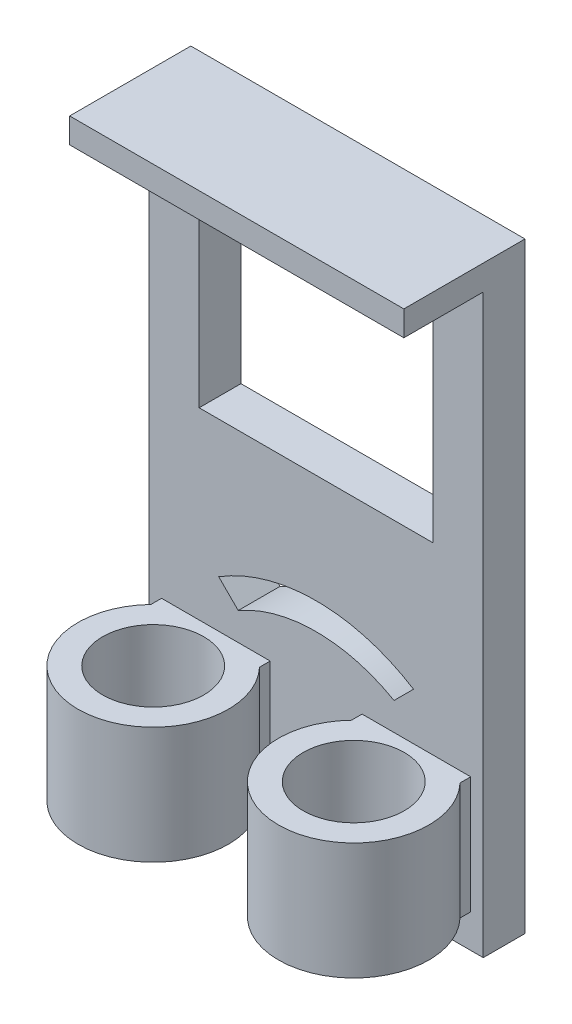
SolidWorks part; units mm, degrees
ref_plane "Front Plane" through (0, 0, 0) normal (0, 0, 1) x (1, 0, 0)
ref_plane "Top Plane" through (0, 0, 0) normal (0, 1, 0) x (1, 0, 0)
ref_plane "Right Plane" through (0, 0, 0) normal (1, 0, 0) x (0, 0, -1)
sketch "Sketch1" plane through (0, 0, 0) normal (0, 0, 1) x (1, 0, 0)
  line L1 (20, -20) -> (-20, -20)
  line L2 (20, -20) -> (20, 20)
  line L3 (20, 20) -> (-20, 20)
  line L4 (-20, -20) -> (-20, 20)
  line L5 (20, -20) -> (-20, 20) construction
  line L6 (20, 20) -> (-20, -20) construction
  point P0 (0, 0)
  dimension "D1" = 40
extrude "Boss-Extrude2" add sketch "Sketch1" along normal blind 2
sketch "Sketch2" plane through (0, 0, 2) normal (0, 0, 1) x (1, 0, 0)
  line L0 (-12, 0) -> (-12, 10) construction
  line L1 (0, 0) -> (-12, 0) construction
  line L2 (-15, 12) -> (-9, 12)
  line L3 (-15, 12) -> (-15, 8)
  line L4 (-15, 8) -> (-9, 8)
  line L5 (-9, 12) -> (-9, 8)
  line L6 (-15, 12) -> (-9, 8) construction
  line L7 (-15, 8) -> (-9, 12) construction
  point P1 (-12, 10)
  dimension "D1" = 10
  dimension "D2" = 4
  dimension "D3" = 6
  dimension "D4" = 12
extrude "Boss-Extrude5" add sketch "Sketch2" along normal blind 3
sketch "Sketch4" plane through (0, 12, 0) normal (0, 1, 0) x (1, 0, 0)
  line L1 (-9, -5) -> (-15, -5) construction
  circle A0 centre (-12, -6.6) radius 1.6
  circle A1 centre (-12, -6.6) radius 3.5
  point P9 (-12, -5)
  dimension "D1" = 3.2
  dimension "D2" = 7
  dimension "D3" = 1.6
extrude "Boss-Extrude6" add sketch "Sketch4" against normal blind 4
ref_plane "Plane2" through (0, 3, 0) normal (0, -1, 0) x (-1, 0, 0)
mirror "Mirror2" about plane through (0, 0, 0) normal (1, 0, 0) of "Boss-Extrude5", "Boss-Extrude6" second plane through (0, 3, 0) second plane normal (0, -1, 0)
sketch "Sketch6" plane through (0, 0, 2) normal (0, 0, 1) x (1, 0, 0)
  line L0 (-20, 20) -> (-15, 20)
  line L1 (20, 20) -> (-20, 20) construction
  line L2 (-15, 20) -> (-15, -20)
  line L3 (-20, -20) -> (20, -20) construction
  line L4 (-15, -20) -> (-20, -20)
  line L5 (-20, -20) -> (-20, 20)
  line L6 (20, 20) -> (15, 20)
  line L7 (15, 20) -> (15, -20)
  line L8 (15, -20) -> (20, -20)
  line L9 (20, -20) -> (20, 20)
  dimension "D1" = 5
  dimension "D2" = 5
  dimension "D4" = 5
extrude "Cut-Extrude1" [suppressed] cut sketch "Sketch6" against normal blind 3 contours L5 L0 L2 L4 | L9 L6 L7 L8
sketch "Sketch7" plane through (0, 0, 2) normal (0, 0, 1) x (1, 0, 0)
  line L0 (0, 0) -> (0, -15)
  line L1 (0, 0) -> (0, 7) construction
  line L2 (-8, 0) -> (8, 0) construction
  line L3 (9.3246, 1.3246) -> (11.6575, 3.6575)
  line L4 (-9.3246, 1.3246) -> (-11.6575, 3.6575)
  line L5 (-8, 0) -> (-9.3246, 1.3246) construction
  line L6 (8, 0) -> (9.3246, 1.3246) construction
  arc A0 (11.6575, 3.6575) -> (-11.6575, 3.6575) centre (0, -15) ccw
  arc A1 (9.3246, 1.3246) -> (-9.3246, 1.3246) centre (0, -15) ccw
  arc A2 (-9.3246, 1.3246) -> (9.3246, 1.3246) centre (0, -15) ccw construction
  arc A3 (-11.6575, 3.6575) -> (11.6575, 3.6575) centre (0, -15) ccw construction
  point P9 (0, 0)
  dimension "D1" = 15
  dimension "D2" = 7
  dimension "D3" = 3.2
  dimension "D4" = 8
  dimension "D5" = 45
  dimension "D6" = 45
extrude "Cut-Extrude2" cut sketch "Sketch7" against normal blind 2 contours A1 L3 A0 L4 region at (0, 4.477, 2)
sketch "Sketch8" plane through (0, 0, 0) normal (0, 0, -1) x (-1, 0, 0)
  line L0 (0, 0) -> (0, -10) construction
  circle A0 centre (0, -10) radius 1.6
  dimension "D1" = 10
  dimension "D2" = 3.2
extrude "Cut-Extrude3" cut sketch "Sketch8" against normal blind 2
sketch "Sketch18" plane through (0, 20, 0) normal (0, 1, 0) x (1, 0, 0)
  line L0 (20, -2) -> (-20, -2) construction
  line L1 (-20, 0) -> (-14, 0)
  line L2 (-20, 0) -> (-20, -2)
  line L3 (-20, -2) -> (-14, -2)
  line L4 (-14, 0) -> (-14, -2)
  line L6 (20, -2) -> (14, -2)
  line L7 (20, -2) -> (20, 0)
  line L8 (20, 0) -> (14, 0)
  line L9 (14, -2) -> (14, 0)
  line L10 (20, 0) -> (-20, 0) construction
  line M5 (20, 0) -> (-20, 0)
  line M6 (-20, 0) -> (-20, -2)
  line M7 (-20, -2) -> (20, -2)
  line M8 (20, -2) -> (20, 0)
  dimension "D2" = 6
  dimension "D1" = 6
extrude "Boss-Extrude10" add sketch "Sketch18" along normal blind 32 contours M7 M8 M5 | M6 M7 region at (-17, 20, 1) region at (17, 20, 1)
sketch "Sketch19" plane through (0, 52, 0) normal (0, 1, 0) x (1, 0, 0)
  line L13 (-20, 0) -> (20, 0)
  line L14 (-20, 0) -> (-20, -3.5)
  line L15 (-20, -3.5) -> (20, -3.5)
  line L16 (20, 0) -> (20, -3.5)
  line M10 (-14, 0) -> (-20, 0)
  line M11 (-20, 0) -> (-20, -2)
  line M12 (-20, -2) -> (-14, -2)
  dimension "D2" = 40
  dimension "D1" = 3.5
extrude "Boss-Extrude11" add sketch "Sketch19" against normal blind 3 contours M12 | M12 M10 M11 region at (0, 52, 1.75)
sketch "Sketch20" plane through (0, -6, 0) normal (0, -1, 0) x (1, 0, 0)
  line L3 (-9, 2) -> (-9, 4.7972)
  line L4 (-15, 4.7972) -> (-15, 2)
  line L5 (-15, 2) -> (-9, 2)
  line L6 (-9, 2) -> (-9, 4.7972)
  line L7 (-15, 4.7972) -> (-15, 2)
  line L8 (-15, 2) -> (-9, 2)
  line L9 (9, 4.7972) -> (9, 2)
  line L10 (9, 2) -> (15, 2)
  line L11 (15, 2) -> (15, 4.7972)
  line L12 (9, 4.7972) -> (9, 2)
  line L13 (9, 2) -> (15, 2)
  line L14 (15, 2) -> (15, 4.7972)
  circle A0 centre (-12, 6.6) radius 1.6 construction
  arc A1 (-9, 4.7972) -> (-15, 4.7972) centre (-12, 6.6) ccw
  arc A2 (-9, 4.7972) -> (-15, 4.7972) centre (-12, 6.6) ccw
  arc A3 (15, 4.7972) -> (9, 4.7972) centre (12, 6.6) ccw
  arc A4 (15, 4.7972) -> (9, 4.7972) centre (12, 6.6) ccw
  circle A5 centre (-12, 6.6) radius 1.6
  circle A6 centre (12, 6.6) radius 1.6 construction
  circle A7 centre (12, 6.6) radius 1.6
  dimension "D1" = 0
  dimension "D2" = 0
extrude "Boss-Extrude12" add sketch "Sketch20" along normal blind 10
sketch "Sketch21" plane through (0, 12, 0) normal (0, 1, 0) x (1, 0, 0)
  line L0 (9, -2) -> (9, -4.7972) construction
  line L1 (15, -4.7972) -> (15, -2) construction
  line L2 (15, -2) -> (9, -2) construction
  line L3 (-9, -4.7972) -> (-9, -2) construction
  line L4 (-9, -2) -> (-15, -2) construction
  line L5 (-15, -2) -> (-15, -4.7972) construction
  line L6 (9, -2) -> (9, -4.7972)
  line L7 (15, -4.7972) -> (15, -2)
  line L8 (15, -2) -> (9, -2)
  line L9 (-9, -4.7972) -> (-9, -2)
  line L10 (-9, -2) -> (-15, -2)
  line L11 (-15, -2) -> (-15, -4.7972)
  arc A0 (9, -4.7972) -> (15, -4.7972) centre (12, -6.6) ccw construction
  arc A1 (-15, -4.7972) -> (-9, -4.7972) centre (-12, -6.6) ccw construction
  circle A2 centre (-12, -6.6) radius 1.6 construction
  circle A3 centre (12, -6.6) radius 1.6 construction
  arc A4 (9, -4.7972) -> (15, -4.7972) centre (12, -6.6) ccw
  arc A5 (-15, -4.7972) -> (-9, -4.7972) centre (-12, -6.6) ccw
  circle A6 centre (-12, -6.6) radius 1.6
  circle A7 centre (12, -6.6) radius 1.6
sketch "Sketch22" plane through (0, -2, 0) normal (0, 1, 0) x (1, 0, 0)
  line L3 (9, -2) -> (9, -4.7972)
  line L4 (15, -4.7972) -> (15, -2)
  line L5 (15, -2) -> (9, -2)
  line L6 (9, -2) -> (9, -4.7972)
  line L7 (15, -4.7972) -> (15, -2)
  line L8 (15, -2) -> (9, -2)
  line L9 (-9, -4.7972) -> (-9, -2)
  line L10 (-9, -2) -> (-15, -2)
  line L11 (-15, -2) -> (-15, -4.7972)
  line L12 (-9, -4.7972) -> (-9, -2)
  line L13 (-9, -2) -> (-15, -2)
  line L14 (-15, -2) -> (-15, -4.7972)
  circle A0 centre (12, -6.6) radius 1.6 construction
  arc A1 (9, -4.7972) -> (15, -4.7972) centre (12, -6.6) ccw
  arc A2 (9, -4.7972) -> (15, -4.7972) centre (12, -6.6) ccw
  circle A3 centre (12, -6.6) radius 1.6
  circle A4 centre (-12, -6.6) radius 1.6 construction
  arc A5 (-15, -4.7972) -> (-9, -4.7972) centre (-12, -6.6) ccw
  arc A6 (-15, -4.7972) -> (-9, -4.7972) centre (-12, -6.6) ccw
  circle A7 centre (-12, -6.6) radius 1.6
  dimension "D1" = 0
  dimension "D2" = 0
extrude "Cut-Extrude4" cut sketch "Sketch22" against normal blind 7
sketch "Sketch23" plane through (0, -16, 0) normal (0, -1, 0) x (1, 0, 0)
  line L0 (-15, 2) -> (-9, 2) construction
  line L1 (-20, 2) -> (20, 2) construction
  line L2 (-15, 2) -> (-9, 2)
  line L3 (-17, 2) -> (-7, 2)
  line L4 (-7, 2) -> (-7, 3.9098)
  line L5 (-17, 2) -> (-17, 3.9098)
  line L6 (0, -5.555) -> (0, 5.555) construction
  line L7 (17, 2) -> (17, 3.9098)
  line L8 (7, 2) -> (7, 3.9098)
  line L9 (17, 2) -> (7, 2)
  line L10 (15, 2) -> (9, 2)
  circle A0 centre (-12, 9.5) radius 6.05
  arc A1 (-7, 3.9098) -> (-17, 3.9098) centre (-12, 9.5) ccw
  arc A2 (7, 3.9098) -> (17, 3.9098) centre (12, 9.5) cw
  circle A3 centre (12, 9.5) radius 6.05
  point P10 (-12, 2)
  point P11 (-12, 2)
  line M8 (-15, 2) -> (-9, 2)
  line M9 (-9, 2) -> (-9, 4.7972)
  line M11 (-15, 4.7972) -> (-15, 2)
  dimension "D1" = 12.1
  dimension "D2" = 15
  dimension "D3" = 10
extrude "Boss-Extrude14" add sketch "Sketch23" against normal blind 14 contours L4 A1 L5 L3 A0 M11 M9 | A0 M11 M8 M9 | A2 L8 L9 L7 A3 region at (-12, -16, 2.8701) region at (-16, -16, 2.2121) region at (16, -16, 2.2121)
extrude "Cut-Extrude5" cut sketch "Sketch21" against normal blind 10
sketch "Sketch24" plane through (0, -9, 0) normal (0, 1, 0) x (1, 0, 0)
  line L2 (9, -4.2462) -> (9, -4.7972)
  line L3 (15, -4.7972) -> (15, -4.2462)
  line L4 (9, -4.2462) -> (9, -4.7972)
  line L5 (15, -4.7972) -> (15, -4.2462)
  line L6 (-9, -4.7972) -> (-9, -4.2462)
  line L7 (-15, -4.2462) -> (-15, -4.7972)
  line L8 (-9, -4.7972) -> (-9, -4.2462)
  line L9 (-15, -4.2462) -> (-15, -4.7972)
  arc A2 (15, -4.2462) -> (9, -4.2462) centre (12, -9.5) ccw
  arc A3 (9, -4.7972) -> (15, -4.7972) centre (12, -6.6) ccw
  arc A4 (15, -4.2462) -> (9, -4.2462) centre (12, -9.5) ccw
  arc A5 (9, -4.7972) -> (15, -4.7972) centre (12, -6.6) ccw
  arc A6 (-9, -4.2462) -> (-15, -4.2462) centre (-12, -9.5) ccw
  arc A7 (-15, -4.7972) -> (-9, -4.7972) centre (-12, -6.6) ccw
  arc A8 (-9, -4.2462) -> (-15, -4.2462) centre (-12, -9.5) ccw
  arc A9 (-15, -4.7972) -> (-9, -4.7972) centre (-12, -6.6) ccw
  dimension "D1" = 0
  dimension "D2" = 0
extrude "Cut-Extrude7" cut sketch "Sketch24" against normal blind 22
sketch "Sketch25" plane through (0, -16, 0) normal (0, -1, 0) x (1, 0, 0)
  line L3 (-17, 2) -> (-7, 2)
  line L4 (-7, 2) -> (-7, 3.9098)
  line L5 (-17, 3.9098) -> (-17, 2)
  line L6 (-17, 2) -> (-7, 2)
  line L7 (-7, 2) -> (-7, 3.9098)
  line L8 (-17, 3.9098) -> (-17, 2)
  line L12 (7, 3.9098) -> (7, 2)
  line L13 (7, 2) -> (17, 2)
  line L14 (17, 2) -> (17, 3.9098)
  line L15 (7, 3.9098) -> (7, 2)
  line L16 (7, 2) -> (17, 2)
  line L17 (17, 2) -> (17, 3.9098)
  arc A1 (-7, 3.9098) -> (-17, 3.9098) centre (-12, 9.5) ccw
  arc A2 (-7, 3.9098) -> (-17, 3.9098) centre (-12, 9.5) ccw
  arc A4 (17, 3.9098) -> (7, 3.9098) centre (12, 9.5) ccw
  arc A5 (17, 3.9098) -> (7, 3.9098) centre (12, 9.5) ccw
  dimension "D1" = 0
  dimension "D2" = 0
sketch "Sketch26" plane through (0, -2, 0) normal (0, 1, 0) x (1, 0, 0)
  line L0 (-16, -2) -> (-8, -2) construction
  line L1 (-16, -2) -> (-16, -6.5)
  line L2 (-8, -2) -> (-8, -6.5)
  line L3 (-7, -2) -> (-17, -2)
  line L4 (-17, -2) -> (-17, -3.9098)
  line L5 (-7, -3.9098) -> (-7, -2)
  line L6 (-7, -2) -> (-17, -2)
  line L8 (-7, -3.9098) -> (-7, -2)
  line L9 (-16, -2) -> (-8, -2)
  line L10 (0, -9.35) -> (0, 9.35) construction
  line L11 (16, -2) -> (16, -6.5)
  line L12 (16, -2) -> (8, -2)
  line L13 (8, -2) -> (8, -6.5)
  circle A0 centre (-12, -9.5) radius 3.15
  arc A1 (-17, -3.9098) -> (-7, -3.9098) centre (-12, -9.5) ccw
  arc A3 (-16, -6.5) -> (-8, -6.5) centre (-12, -9.5) ccw
  circle A4 centre (12, -9.5) radius 3.15
  arc A5 (16, -6.5) -> (8, -6.5) centre (12, -9.5) cw
  point P10 (-12, -2)
  circle M14 centre (-12, -9.5) radius 6.05
  dimension "D2" = 6.3
  dimension "D3" = 10
  dimension "D4" = 4.5
  dimension "D1" = 0
extrude "Boss-Extrude17" [suppressed] add sketch "Sketch26" along normal blind 15 contours A5 L11 L12 L13 A4 | L1 A3 L2 A0 M14 | A3 L2 L9 L1 | A0
sketch "Sketch30" [suppressed] plane through (-20, 0, 0) normal (-1, 0, 0) x (0, 0, 1)
  line L1 (2, -6) -> (14.5, -6)
  line L2 (2, -6) -> (2, 4)
  line L3 (2, 4) -> (14.5, 4)
  line L4 (14.5, -6) -> (14.5, 4)
  line L5 (14.5, -6) -> (14.5, 9) construction
  dimension "D1" = 10
  dimension "D2" = 12.5
extrude "Cut-Extrude8" [suppressed] cut sketch "Sketch30" against normal blind 43
extrude "Cut-Extrude9" cut sketch "Sketch25" against normal blind 2
sketch "Sketch32" plane through (0, -14, 0) normal (0, -1, 0) x (1, 0, 0)
  line L3 (7, 3.9098) -> (7, 2)
  line L4 (7, 2) -> (17, 2)
  line L5 (17, 2) -> (17, 3.9098)
  line L6 (7, 3.9098) -> (7, 2)
  line L7 (7, 2) -> (17, 2)
  line L8 (17, 2) -> (17, 3.9098)
  line L9 (-17, 3.9098) -> (-17, 2)
  line L10 (-17, 2) -> (-7, 2)
  line L11 (-7, 2) -> (-7, 3.9098)
  line L12 (-17, 3.9098) -> (-17, 2)
  line L13 (-17, 2) -> (-7, 2)
  line L14 (-7, 2) -> (-7, 3.9098)
  circle A0 centre (-12, 9.5) radius 3.5
  arc A1 (17, 3.9098) -> (7, 3.9098) centre (12, 9.5) ccw
  arc A2 (17, 3.9098) -> (7, 3.9098) centre (12, 9.5) ccw
  arc A3 (-7, 3.9098) -> (-17, 3.9098) centre (-12, 9.5) ccw
  arc A4 (-7, 3.9098) -> (-17, 3.9098) centre (-12, 9.5) ccw
  circle A5 centre (12, 9.5) radius 3.5
  dimension "D3" = 7
  dimension "D4" = 7
  dimension "D1" = 0
  dimension "D2" = 0
extrude "Boss-Extrude19" add sketch "Sketch32" along normal blind 2
sketch "Sketch33" plane through (0, 0, 3.5) normal (0, 0, 1) x (1, 0, 0)
  line L4 (20, 52) -> (-20, 52)
  line L5 (-20, 52) -> (-20, 49)
  line L6 (-20, 49) -> (20, 49)
  line L7 (20, 49) -> (20, 52)
  line L8 (20, 52) -> (-20, 52)
  line L9 (-20, 52) -> (-20, 49)
  line L10 (-20, 49) -> (20, 49)
  line L11 (20, 49) -> (20, 52)
  dimension "D1" = 0
extrude "Boss-Extrude20" add sketch "Sketch33" along normal blind 8
sketch "Sketch34" plane through (0, 0, 0) normal (0, 0, -1) x (-1, 0, 0)
  line L0 (-9.3246, 1.3246) -> (-11.6575, 3.6575) construction
  line L1 (-14, 49) -> (-14, 20) construction
  line L2 (14, 49) -> (-14, 49) construction
  line L3 (14, 49) -> (14, 20) construction
  line L4 (20, -20) -> (20, 52)
  line L5 (20, 52) -> (-20, 52)
  line L6 (-20, 52) -> (-20, -20)
  line L7 (-20, -20) -> (20, -20)
  line L8 (20, -20) -> (20, 52)
  line L9 (20, 52) -> (-20, 52)
  line L10 (-20, 52) -> (-20, -20)
  line L11 (-20, -20) -> (20, -20)
  line L12 (-14, 20) -> (14, 20) construction
  line L13 (-9.3246, 1.3246) -> (-11.6575, 3.6575)
  line L14 (-14, 49) -> (-14, 20)
  line L15 (14, 49) -> (-14, 49)
  line L16 (14, 49) -> (14, 20)
  line L17 (-14, 20) -> (14, 20)
  circle A0 centre (0, -10) radius 1.6 construction
  arc A1 (9.3246, 1.3246) -> (-9.3246, 1.3246) centre (0, -15) ccw construction
  arc A2 (11.6575, 3.6575) -> (-11.6575, 3.6575) centre (0, -15) ccw construction
  circle A3 centre (0, -10) radius 1.6
  arc A4 (9.3246, 1.3246) -> (-9.3246, 1.3246) centre (0, -15) ccw
  arc A5 (11.6575, 3.6575) -> (-11.6575, 3.6575) centre (0, -15) ccw
  line M5 (-14, 20) -> (-14, 49)
  line M6 (-14, 49) -> (14, 49)
  line M7 (14, 49) -> (14, 20)
  line M8 (14, 20) -> (-14, 20)
  line M9 (20, -20) -> (20, 52)
  line M10 (20, 52) -> (-20, 52)
  line M11 (-20, 52) -> (-20, -20)
  line M12 (-20, -20) -> (20, -20)
  circle M13 centre (0, -10) radius 1.6
  arc M14 (9.3246, 1.3246) -> (-9.3246, 1.3246) centre (0, -15) ccw
  line M15 (-9.3246, 1.3246) -> (-11.6575, 3.6575)
  arc M16 (-11.6575, 3.6575) -> (11.6575, 3.6575) centre (0, -15) cw
  line M17 (11.6575, 3.6575) -> (9.3246, 1.3246)
  dimension "D1" = 0
extrude "Boss-Extrude21" add sketch "Sketch34" along normal blind 3 contours M12 M9 M10 M11 M13 M17 M14 M15 M16 M8 M5 M6 M7 region at (0, 8.9627, 0)
sketch "Sketch35" plane through (0, -16, 0) normal (0, -1, 0) x (1, 0, 0)
  line L0 (-18.5, 3.2751) -> (-18.5, 0.5)
  line L1 (-18.5, 0.5) -> (-5.5, 0.5)
  line L2 (-5.5, 0.5) -> (-5.5, 3.2751)
  line L3 (-17, 3.9098) -> (-17, 2)
  line L4 (-17, 2) -> (-7, 2)
  line L5 (-7, 2) -> (-7, 3.9098)
  line L6 (-17, 3.9098) -> (-17, 2)
  line L7 (-17, 2) -> (-7, 2)
  line L8 (-7, 2) -> (-7, 3.9098)
  line L9 (7, 3.9098) -> (7, 2)
  line L10 (7, 2) -> (17, 2)
  line L11 (17, 2) -> (17, 3.9098)
  line L12 (7, 3.9098) -> (7, 2)
  line L13 (7, 2) -> (17, 2)
  line L14 (17, 2) -> (17, 3.9098)
  line L15 (5.5, 3.2751) -> (5.5, 0.5)
  line L16 (5.5, 0.5) -> (18.5, 0.5)
  line L17 (18.5, 0.5) -> (18.5, 3.2751)
  arc A0 (-5.5, 3.2751) -> (-18.5, 3.2751) centre (-12, 9.5) ccw
  arc A1 (-7, 3.9098) -> (-17, 3.9098) centre (-12, 9.5) ccw
  arc A2 (-7, 3.9098) -> (-17, 3.9098) centre (-12, 9.5) ccw
  arc A3 (17, 3.9098) -> (7, 3.9098) centre (12, 9.5) ccw
  arc A4 (17, 3.9098) -> (7, 3.9098) centre (12, 9.5) ccw
  arc A5 (18.5, 3.2751) -> (5.5, 3.2751) centre (12, 9.5) ccw
  dimension "D1" = 0
  dimension "D2" = 0
  dimension "D3" = 1.5
extrude "Boss-Extrude22" add sketch "Sketch35" against normal up to surface (14 mm away) up to face at (-12, -2, 6.2275)
sketch "Sketch38" plane through (0, -16, 0) normal (0, -1, 0) x (1, 0, 0)
  line L0 (-19.4833, 14.5) -> (-4.5167, 14.5) construction
  line L1 (4.5167, 14.5) -> (19.4833, 14.5) construction
  line L2 (-12, 9.5) -> (-19.4833, 14.5)
  line L3 (-18.5, 3.2751) -> (-18.5, 2)
  line L4 (-18.5, 2) -> (-5.5, 2)
  line L5 (-5.5, 2) -> (-5.5, 3.2751)
  line L6 (-18.5, 3.2751) -> (-18.5, 2) construction
  line L7 (-18.5, 2) -> (-5.5, 2) construction
  line L8 (-5.5, 2) -> (-5.5, 3.2751) construction
  line L9 (5.5, 3.2751) -> (5.5, 2)
  line L10 (5.5, 2) -> (18.5, 2)
  line L11 (18.5, 2) -> (18.5, 3.2751)
  line L12 (5.5, 3.2751) -> (5.5, 2) construction
  line L13 (5.5, 2) -> (18.5, 2) construction
  line L14 (18.5, 2) -> (18.5, 3.2751) construction
  line L15 (-12, 9.5) -> (-4.5167, 14.5)
  line L16 (12, 9.5) -> (4.5167, 14.5)
  line L17 (12, 9.5) -> (19.4833, 14.5)
  arc A1 (-5.5, 3.2751) -> (-18.5, 3.2751) centre (-12, 9.5) ccw
  arc A2 (-4.5167, 14.5) -> (-19.4833, 14.5) centre (-12, 9.5) ccw
  arc A3 (18.5, 3.2751) -> (5.5, 3.2751) centre (12, 9.5) ccw
  arc A4 (19.4833, 14.5) -> (4.5167, 14.5) centre (12, 9.5) ccw
  arc A7 (-19.4833, 14.5) -> (-18.5, 3.2751) centre (-12, 9.5) ccw construction
  arc A8 (-5.5, 3.2751) -> (-4.5167, 14.5) centre (-12, 9.5) ccw construction
  arc A9 (4.5167, 14.5) -> (5.5, 3.2751) centre (12, 9.5) ccw construction
  arc A10 (18.5, 3.2751) -> (19.4833, 14.5) centre (12, 9.5) ccw construction
  point P13 (-12, 14.5)
  point P16 (12, 14.5)
  dimension "D3" = 5
  dimension "D1" = 0
  dimension "D2" = 0
